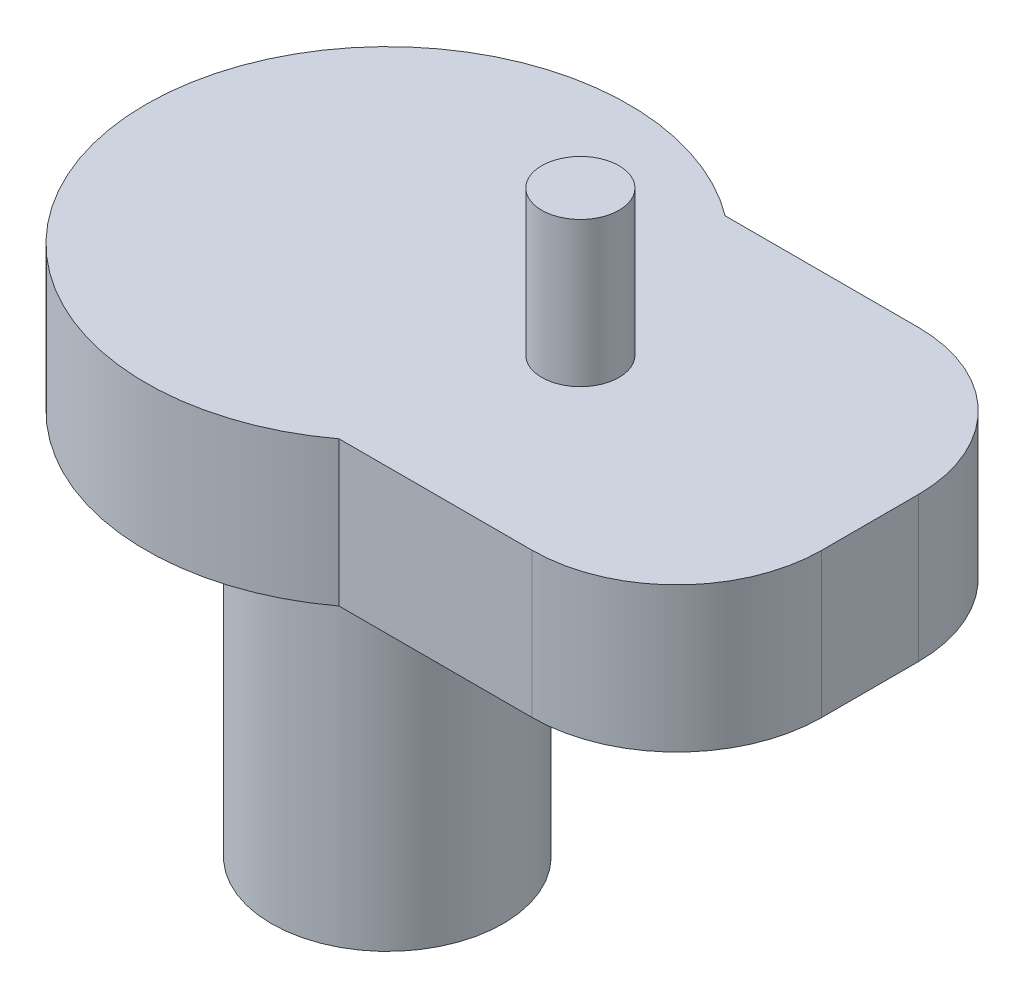
SolidWorks part; units mm, degrees
ref_plane "Front Plane" through (0, 0, 0) normal (0, 0, 1) x (1, 0, 0)
ref_plane "Top Plane" through (0, 0, 0) normal (0, 1, 0) x (1, 0, 0)
ref_plane "Right Plane" through (0, 0, 0) normal (1, 0, 0) x (0, 0, -1)
sketch "Sketch1" plane through (0, 0, 0) normal (0, 1, 0) x (1, 0, 0)
  line L1 (-7.5, -7.5) -> (7.5, -7.5)
  line L2 (-7.5, -7.5) -> (-7.5, 7.5)
  line L3 (-7.5, 7.5) -> (7.5, 7.5)
  line L4 (7.5, -7.5) -> (7.5, 7.5)
  line L5 (-7.5, -7.5) -> (7.5, 7.5) construction
  line L6 (-7.5, 7.5) -> (7.5, -7.5) construction
  circle A0 centre (0, 0) radius 25
  circle A1 centre (0, 0) radius 12
  dimension "D1" = 50
  dimension "D4" = 24
  dimension "D2" = 15
  dimension "D3" = 15
extrude "Boss-Extrude1" add sketch "Sketch1" along normal blind 15 contours A0
extrude "Boss-Extrude2" add sketch "Sketch1<3>" against normal blind 40 contours A1
sketch "Sketch1<3>" plane through (0, 0, 0) normal (0, 1, 0) x (1, 0, 0) same geometry as "Sketch1"
sketch "Sketch4" plane through (0, 0, 0) normal (1, 0, 0) x (0, 0, -1)
  line L0 (-20, 0) -> (20, 0)
  line L1 (25, 0) -> (-25, 0) construction
  line L2 (20, 0) -> (20, 15)
  line L3 (25, 15) -> (-25, 15) construction
  line L4 (20, 15) -> (-20, 15)
  line L6 (0, 0) -> (0, 46.2195) construction
  line L7 (-20, 0) -> (-20, 15)
  dimension "D1" = 20
extrude "Boss-Extrude4" add sketch "Sketch4" against normal up to surface (35 mm away) from offset 50 up to face at (0, 15, 25)
fillet "Fillet2" radius 15 2 edges at (50, 7.5, -20) (50, 7.5, 20)
sketch "Sketch7" plane through (0, 0, 0) normal (0, 1, 0) x (1, 0, 0)
  line L0 (0, 0) -> (20, 0) construction
  circle A0 centre (20, 0) radius 4
  dimension "D2" = 8
  dimension "D1" = 20
extrude "Boss-Extrude8" add sketch "Sketch7" along normal blind 15 from surface starting at face at (27.7022, 15, 0)
